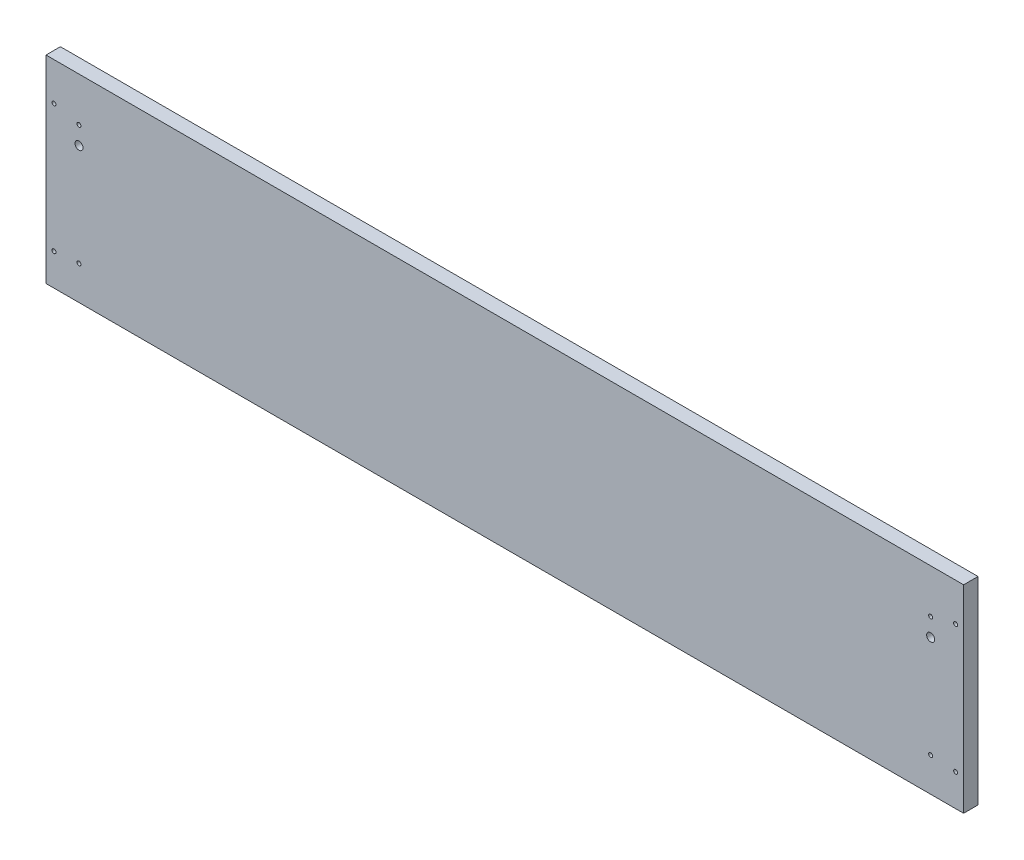
SolidWorks part; units mm, degrees
material "Pine"
ref_plane "Front Plane" through (0, 0, 0) normal (0, 0, 1) x (1, 0, 0)
ref_plane "Top Plane" through (0, 0, 0) normal (0, 1, 0) x (1, 0, 0)
ref_plane "Right Plane" through (0, 0, 0) normal (1, 0, 0) x (0, 0, -1)
sketch "Sketch1" plane through (0, 0, 0) normal (0, 0, 1) x (1, 0, 0)
  line L0 (-5300.6625, 1520.825) -> (-5451.475, 1520.825)
  line L1 (-5456.2375, 1384.3) -> (-5456.2375, 1516.0625)
  line L2 (-5557.8375, 1546.225) -> (-5194.3, 1546.225)
  line L3 (-5557.8375, 1539.875) -> (-5194.3, 1539.875)
  line L4 (-5297.4875, 1377.95) -> (-5454.65, 1377.95)
  line L5 (-5291.1375, 1384.3) -> (-5291.1375, 1516.0625)
  line L6 (-5300.6625, 1525.5875) -> (-5451.475, 1525.5875)
  line L7 (-5461, 1384.3) -> (-5461, 1516.0625)
  line L8 (-5297.4875, 1382.7125) -> (-5454.65, 1382.7125)
  line L9 (-5295.9, 1384.3) -> (-5295.9, 1516.0625)
  line L10 (-5740.4, 998.5375) -> (-5740.4, 1181.1)
  line L11 (-5740.4, 1181.1) -> (-5512.5938, 1181.1)
  line L12 (-5512.5938, 1181.1) -> (-5512.5938, 998.5375)
  line L13 (-5512.5938, 998.5375) -> (-5740.4, 998.5375)
  line L14 (-5258.5938, 1181.1) -> (-5486.4, 1181.1)
  line L15 (-5258.5938, 998.5375) -> (-5258.5938, 1181.1)
  line L16 (-5486.4, 998.5375) -> (-5258.5938, 998.5375)
  line L17 (-5486.4, 1181.1) -> (-5486.4, 998.5375)
  line L18 (-5740.4, 898.525) -> (-5011.7375, 898.525)
  line L19 (-5168.1062, 1384.3) -> (-5168.1062, 1392.2375)
  line L20 (-5176.0437, 1400.175) -> (-5245.8937, 1400.175)
  line L21 (-5253.8313, 1392.2375) -> (-5253.8313, 1384.3)
  line L22 (-5451.475, 1512.8875) -> (-5451.475, 1384.3)
  line L23 (-5303.8375, 1516.0625) -> (-5448.3, 1516.0625)
  line L24 (-5498.3062, 1384.3) -> (-5451.475, 1384.3)
  line L25 (-5253.8313, 1384.3) -> (-5300.6625, 1384.3)
  line L26 (-5584.0312, 1384.3) -> (-5740.4, 1384.3)
  line L27 (-5564.1875, 1536.7) -> (-5740.4, 1536.7)
  line L28 (-5740.4, 1357.3125) -> (-5740.4, 1206.5)
  line L29 (-5011.7375, 1357.3125) -> (-5740.4, 1357.3125)
  line L30 (-5011.7375, 1206.5) -> (-5011.7375, 1357.3125)
  line L31 (-5740.4, 1206.5) -> (-5011.7375, 1206.5)
  line L32 (-4765.675, 1549.4) -> (-4978.4, 1549.4)
  line L33 (-4765.675, 1397) -> (-4765.675, 1549.4)
  line L34 (-4978.4, 1397) -> (-4765.675, 1397)
  line L35 (-4978.4, 1549.4) -> (-4978.4, 1397)
  line L36 (-4765.675, 1371.6) -> (-4978.4, 1371.6)
  line L37 (-4765.675, 1219.2) -> (-4765.675, 1371.6)
  line L38 (-4978.4, 1219.2) -> (-4765.675, 1219.2)
  line L39 (-4978.4, 1371.6) -> (-4978.4, 1219.2)
  line L40 (-5284.7875, 803.275) -> (-5272.0875, 803.275)
  line L41 (-5187.95, 1536.7) -> (-5011.7375, 1536.7)
  line L42 (-5300.6625, 1384.3) -> (-5300.6625, 1512.8875)
  line L43 (-5740.4, 1536.7) -> (-5740.4, 1384.3)
  line L44 (-5557.8375, 1536.7) -> (-5557.8375, 1549.4)
  line L45 (-5557.8375, 1549.4) -> (-5194.3, 1549.4)
  line L46 (-5194.3, 1549.4) -> (-5194.3, 1536.7)
  line L47 (-5011.7375, 1536.7) -> (-5011.7375, 1384.3)
  line L48 (-5011.7375, 1384.3) -> (-5168.1062, 1384.3)
  line L49 (-5498.3062, 1384.3) -> (-5498.3062, 1392.2375)
  line L50 (-5506.2437, 1400.175) -> (-5576.0938, 1400.175)
  line L51 (-5584.0312, 1392.2375) -> (-5584.0312, 1384.3)
  line L52 (-5740.4, 660.4) -> (-5740.4, 898.525)
  line L53 (-5011.7375, 898.525) -> (-5011.7375, 660.4)
  line L54 (-5011.7375, 660.4) -> (-5740.4, 660.4)
  line L55 (-5291.1375, 803.275) -> (-5291.1375, 752.475)
  line L56 (-5265.7375, 752.475) -> (-5265.7375, 803.275)
  line L57 (-5284.7875, 752.475) -> (-5272.0875, 752.475)
  arc A0 (-5451.475, 1520.825) -> (-5456.2375, 1516.0625) centre (-5451.475, 1516.0625) ccw
  arc A1 (-5461, 1384.3) -> (-5454.65, 1377.95) centre (-5454.65, 1384.3) ccw
  arc A2 (-5297.4875, 1377.95) -> (-5291.1375, 1384.3) centre (-5297.4875, 1384.3) ccw
  circle A3 centre (-5037.9312, 1233.4875) radius 1.5875
  circle A4 centre (-5037.9312, 1328.7375) radius 1.5875
  circle A5 centre (-5714.2063, 1233.4875) radius 1.5875
  circle A6 centre (-5714.2063, 1328.7375) radius 1.5875
  circle A7 centre (-5018.0875, 1333.5) radius 1.5875
  circle A8 centre (-5018.0875, 1231.9) radius 1.5875
  circle A9 centre (-5734.05, 1231.9) radius 1.5875
  circle A10 centre (-5734.05, 1333.5) radius 1.5875
  circle A11 centre (-5734.05, 1511.3) radius 1.5875
  circle A12 centre (-5734.05, 1409.7) radius 1.5875
  circle A13 centre (-5018.0875, 1511.3) radius 1.5875
  circle A14 centre (-5018.0875, 1409.7) radius 1.5875
  arc A15 (-5557.8375, 1546.225) -> (-5557.8375, 1539.875) centre (-5557.8375, 1543.05) ccw
  arc A16 (-5194.3, 1539.875) -> (-5194.3, 1546.225) centre (-5194.3, 1543.05) ccw
  arc A17 (-5291.1375, 1516.0625) -> (-5300.6625, 1525.5875) centre (-5300.6625, 1516.0625) ccw
  arc A18 (-5451.475, 1525.5875) -> (-5461, 1516.0625) centre (-5451.475, 1516.0625) ccw
  arc A19 (-5456.2375, 1384.3) -> (-5454.65, 1382.7125) centre (-5454.65, 1384.3) ccw
  arc A20 (-5297.4875, 1382.7125) -> (-5295.9, 1384.3) centre (-5297.4875, 1384.3) ccw
  arc A21 (-5295.9, 1516.0625) -> (-5300.6625, 1520.825) centre (-5300.6625, 1516.0625) ccw
  circle A22 centre (-5702.3, 892.175) radius 1.5875
  circle A23 centre (-5734.05, 860.425) radius 1.5875
  circle A24 centre (-5474.8906, 892.175) radius 1.5875
  circle A25 centre (-5277.2469, 892.175) radius 1.5875
  circle A26 centre (-5049.8375, 892.175) radius 1.5875
  circle A27 centre (-5018.0875, 860.425) radius 1.5875
  circle A28 centre (-5296.6938, 1174.75) radius 1.5875
  circle A29 centre (-5448.3, 1174.75) radius 1.5875
  circle A30 centre (-5264.9437, 1155.7) radius 1.5875
  circle A31 centre (-5264.9437, 1023.9375) radius 1.5875
  circle A32 centre (-5518.9438, 1155.7) radius 1.5875
  circle A33 centre (-5518.9438, 1023.9375) radius 1.5875
  circle A34 centre (-5702.3, 1004.8875) radius 1.5875
  circle A35 centre (-5550.6937, 1004.8875) radius 1.5875
  arc A36 (-5576.0938, 1400.175) -> (-5584.0312, 1392.2375) centre (-5576.0938, 1392.2375) ccw
  arc A37 (-5168.1062, 1392.2375) -> (-5176.0437, 1400.175) centre (-5176.0437, 1392.2375) ccw
  arc A38 (-5245.8937, 1400.175) -> (-5253.8313, 1392.2375) centre (-5245.8937, 1392.2375) ccw
  arc A39 (-5448.3, 1516.0625) -> (-5451.475, 1512.8875) centre (-5448.3, 1512.8875) ccw
  arc A40 (-5284.7875, 803.275) -> (-5291.1375, 803.275) centre (-5287.9625, 803.275) ccw
  circle A41 centre (-5679.2812, 1026.3187) radius 1.5875
  circle A42 centre (-5679.2812, 1153.3187) radius 1.5875
  circle A43 centre (-5571.3313, 1153.3187) radius 1.5875
  circle A44 centre (-5571.3313, 1026.3187) radius 1.5875
  circle A45 centre (-5317.3312, 1153.3187) radius 1.5875
  circle A46 centre (-5317.3312, 1026.3187) radius 1.5875
  circle A47 centre (-5425.2812, 1026.3187) radius 1.5875
  circle A48 centre (-5425.2812, 1153.3187) radius 1.5875
  arc A49 (-5194.3, 1536.7) -> (-5187.95, 1536.7) centre (-5191.125, 1536.7) ccw
  arc A50 (-5564.1875, 1536.7) -> (-5557.8375, 1536.7) centre (-5561.0125, 1536.7) ccw
  arc A51 (-5300.6625, 1512.8875) -> (-5303.8375, 1516.0625) centre (-5303.8375, 1512.8875) ccw
  arc A52 (-5498.3062, 1392.2375) -> (-5506.2437, 1400.175) centre (-5506.2437, 1392.2375) ccw
  circle A53 centre (-5712.46, 784.225) radius 4.7625
  arc A54 (-5272.0875, 752.475) -> (-5265.7375, 752.475) centre (-5268.9125, 752.475) ccw
  arc A55 (-5291.1375, 752.475) -> (-5284.7875, 752.475) centre (-5287.9625, 752.475) ccw
  circle A56 centre (-5182.3938, 684.2125) radius 3.175
  circle A57 centre (-5239.5437, 684.2125) radius 3.175
  circle A58 centre (-5512.5938, 684.2125) radius 3.175
  circle A59 centre (-5569.7437, 684.2125) radius 3.175
  circle A60 centre (-5474.8906, 666.75) radius 1.5875
  circle A61 centre (-5277.2469, 666.75) radius 1.5875
  circle A62 centre (-5734.05, 698.5) radius 1.5875
  circle A63 centre (-5702.3, 666.75) radius 1.5875
  circle A64 centre (-5049.8375, 666.75) radius 1.5875
  circle A65 centre (-5018.0875, 698.5) radius 1.5875
  circle A66 centre (-5713.73, 835.025) radius 4.7625
  circle A67 centre (-5712.46, 819.785) radius 4.7625
  circle A68 centre (-5712.46, 802.005) radius 4.7625
  circle A69 centre (-5714.2063, 1314.45) radius 3.175
  circle A70 centre (-5037.9312, 1314.45) radius 3.175
  arc A71 (-5265.7375, 803.275) -> (-5272.0875, 803.275) centre (-5268.9125, 803.275) ccw
  ellipse E0 centre (-5371.3062, 1089.8188) end of major axis (-5277.6438, 1089.8188) minor radius 65.0875
  ellipse E1 centre (-5625.3062, 1089.8188) end of major axis (-5531.6438, 1089.8188) minor radius 65.0875
sketch "LidOutline" plane through (0, 0, 0) normal (0, 0, 1) x (1, 0, 0)
  line L0 (-5011.7375, 1206.5) -> (-5011.7375, 1363.6625)
  line L1 (-5011.7375, 1363.6625) -> (-5740.4, 1363.6625)
  line L2 (-5740.4, 1363.6625) -> (-5740.4, 1206.5)
  line L3 (-5740.4, 1206.5) -> (-5011.7375, 1206.5)
  line L4 (-5376.0688, 1206.5) -> (-5376.0688, 1363.6625) construction
  line L5 (-5376.0688, 1285.0812) -> (-5740.4, 1285.0812) construction
  line L6 (-5376.0688, 1285.0812) -> (-5011.7375, 1285.0812) construction
  dimension "Width" = 157.1625
  dimension "Lendth" = 728.6625
extrude "LidOutline_Thickness" add sketch "LidOutline" against normal blind 11.43
sketch "Lid_MountingHoles" plane through (0, 0, 0) normal (0, 0, 1) x (1, 0, 0)
  circle A0 centre (-5714.2063, 1314.45) radius 3.175
  circle A1 centre (-5714.2063, 1328.7375) radius 1.5875
  circle A2 centre (-5734.05, 1333.5) radius 1.5875
  circle A3 centre (-5734.05, 1231.9) radius 1.5875
  circle A4 centre (-5714.2063, 1233.4875) radius 1.5875
  circle A5 centre (-5037.9312, 1314.45) radius 3.175
  circle A6 centre (-5037.9312, 1328.7375) radius 1.5875
  circle A7 centre (-5018.0875, 1333.5) radius 1.5875
  circle A8 centre (-5037.9312, 1233.4875) radius 1.5875
  circle A9 centre (-5018.0875, 1231.9) radius 1.5875
extrude "Cut-Extrude1" cut sketch "Lid_MountingHoles" against normal up to surface (11.43 mm away) up to face at (-5376.0688, 1285.0812, -11.43)
